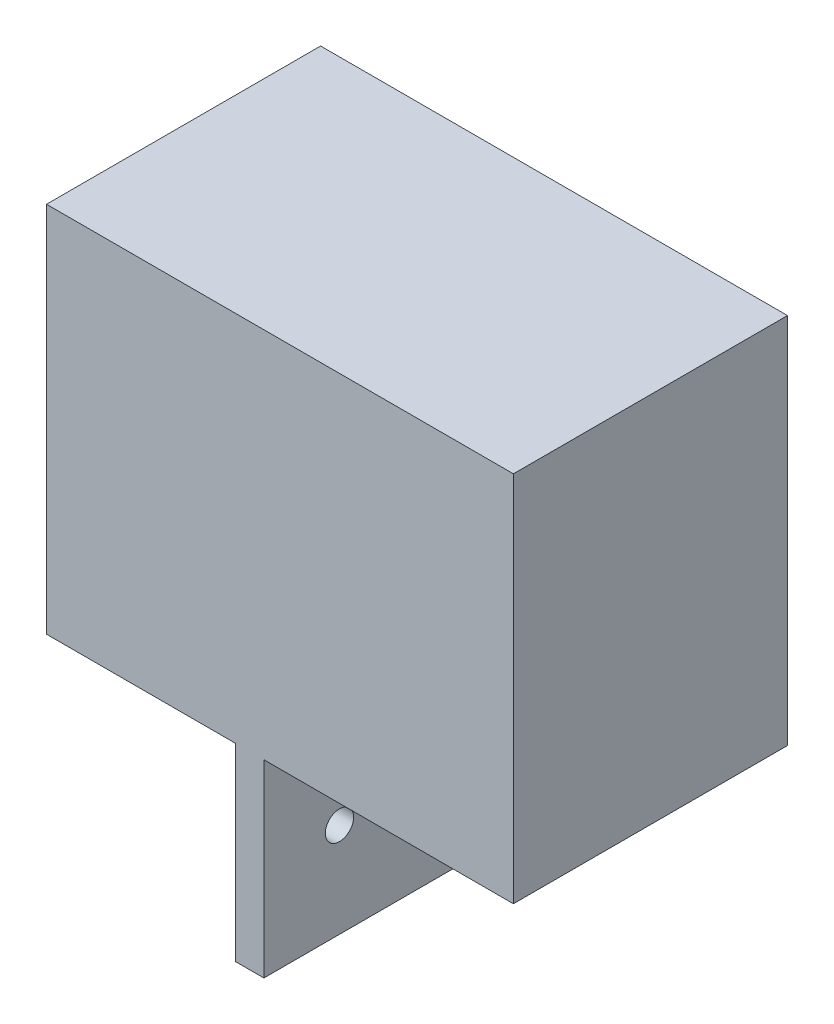
SolidWorks part; units mm, degrees
ref_plane "Front Plane" through (0, 0, 0) normal (0, 0, 1) x (1, 0, 0)
ref_plane "Top Plane" through (0, 0, 0) normal (0, 1, 0) x (1, 0, 0)
ref_plane "Right Plane" through (0, 0, 0) normal (1, 0, 0) x (0, 0, -1)
sketch "Sketch2" plane through (0, 0, 0) normal (0, 0, 1) x (1, 0, 0)
  line L1 (0, 0) -> (42.418, 0)
  line L2 (0, 0) -> (0, 42.418)
  line L3 (0, 42.418) -> (42.418, 42.418)
  line L4 (42.418, 0) -> (42.418, 42.418)
  line L5 (-3.81, 46.228) -> (46.228, 46.228)
  line L6 (-3.81, 46.228) -> (-3.81, -3.81)
  line L7 (-3.81, -3.81) -> (46.228, -3.81)
  line L8 (46.228, 46.228) -> (46.228, -3.81)
  dimension "D1" = 42.418
  dimension "D2" = 42.418
  dimension "D3" = 3.81
  dimension "D4" = 3.81
  dimension "D5" = 3.81
  dimension "D6" = 3.81
extrude "Boss-Extrude1" add sketch "Sketch2" along normal blind 34.29
sketch "Sketch4" plane through (0, 0, 34.29) normal (0, 0, 1) x (1, 0, 0)
  line L1 (-3.81, 46.228) -> (46.228, 46.228)
  line L2 (-3.81, 46.228) -> (-3.81, -3.81)
  line L3 (-3.81, -3.81) -> (46.228, -3.81)
  line L4 (46.228, 46.228) -> (46.228, -3.81)
extrude "Boss-Extrude2" add sketch "Sketch4" along normal blind 2.54
sketch "Sketch5" plane through (0, 0, 0) normal (0, 0, -1) x (-1, 0, 0)
  line L6 (3.81, -3.81) -> (-46.228, -3.81) construction
  line L7 (-12.7, -3.81) -> (-8.89, -3.81)
  line L8 (-12.7, -3.81) -> (-12.7, -29.21)
  line L9 (-12.7, -29.21) -> (-8.89, -29.21)
  line L10 (-8.89, -3.81) -> (-8.89, -29.21)
  line L11 (3.81, 46.228) -> (3.81, -3.81) construction
  dimension "D1" = 12.7
  dimension "D2" = 3.81
  dimension "D3" = 25.4
extrude "Boss-Extrude3" add sketch "Sketch5" against normal up to surface (36.83 mm away) up to face at (21.209, 21.209, 36.83)
sketch "Sketch6" plane through (0, 0, 0) normal (0, 0, -1) x (-1, 0, 0)
  line L0 (-46.228, 46.228) -> (3.81, 46.228) construction
  line L1 (3.81, -3.81) -> (16.51, -3.81)
  line L2 (3.81, -3.81) -> (3.81, 46.228)
  line L3 (3.81, 46.228) -> (16.51, 46.228)
  line L4 (16.51, -3.81) -> (16.51, 46.228)
  dimension "D1" = 0
  dimension "D2" = 12.7
extrude "Boss-Extrude4" add sketch "Sketch6" against normal up to surface (36.83 mm away) up to face at (16.002, 2.3495, 36.83)
sketch "Sketch7" plane through (12.7, 0, 0) normal (1, 0, 0) x (0, 0, -1)
  line L0 (-36.83, -29.21) -> (0, -29.21) construction
  line L1 (0, -3.81) -> (0, -29.21) construction
  line L2 (-36.83, -3.81) -> (-36.83, -29.21) construction
  circle A0 centre (-26.67, -16.51) radius 1.905
  circle A1 centre (-10.16, -16.51) radius 1.905
  dimension "D1" = 3.81
  dimension "D2" = 3.81
  dimension "D3" = 12.7
  dimension "D4" = 12.7
  dimension "D5" = 10.16
  dimension "D6" = 10.16
extrude "Cut-Extrude1" cut sketch "Sketch7" against normal through all
